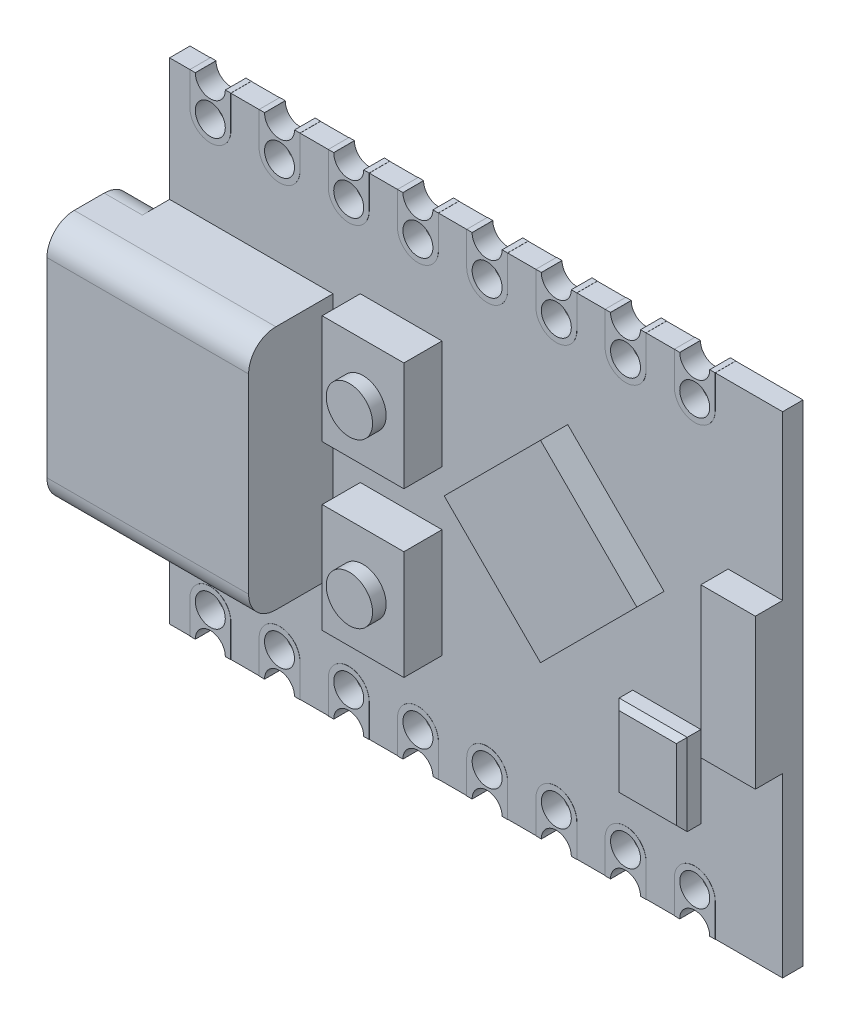
SolidWorks part; units mm, degrees
ref_plane "Plano frontal" through (0, 0, 0) normal (0, 0, 1) x (1, 0, 0)
ref_plane "Plano superior" through (0, 0, 0) normal (0, 1, 0) x (1, 0, 0)
ref_plane "Plano direito" through (0, 0, 0) normal (1, 0, 0) x (0, 0, -1)
sketch "Esboço1" plane through (0, 0, 0) normal (0, 0, 1) x (1, 0, 0)
  line L1 (-22.5, 18) -> (0, 18)
  line L2 (-22.5, 18) -> (-22.5, 0)
  line L3 (-22.5, 0) -> (0, 0)
  line L4 (0, 18) -> (0, 0)
  dimension "D1" = 18
  dimension "D2" = 22.5
extrude "PCI" add sketch "Esboço1" along normal blind 0.75
sketch "Esboço2" plane through (0, 0, 0.75) normal (0, 0, 1) x (1, 0, 0)
  line L0 (-11.4211, 10.1145) -> (-7.8855, 13.65)
  line L1 (-11.4211, 10.1145) -> (-7.8855, 6.5789)
  line L2 (-7.8855, 13.65) -> (-4.35, 10.1145)
  line L3 (-7.8855, 6.5789) -> (-4.35, 10.1145)
  line L4 (0, 0) -> (0, 18) construction
  line L5 (0, 18) -> (-22.5, 18) construction
  dimension "D1" = 45
  dimension "D2" = 4.35
  dimension "D3" = 4.35
  dimension "D4" = 5
extrude "ESP32" add sketch "Esboço2" along normal blind 1
sketch "Esboço3" plane through (0, 0, 0.75) normal (0, 0, 1) x (1, 0, 0)
  line L0 (-22.5, 18) -> (-22.5, 0) construction
  line L1 (-16.5, 13.5) -> (-23.9, 13.5)
  line L2 (-16.5, 13.5) -> (-16.5, 4.5)
  line L3 (-16.5, 4.5) -> (-23.9, 4.5)
  line L4 (-23.9, 13.5) -> (-23.9, 4.5)
  line L5 (-22.5, 9) -> (0, 9) construction
  line L6 (0, 0) -> (0, 18) construction
  dimension "D1" = 1.4
  dimension "D2" = 7.4
  dimension "D3" = 4.5
  dimension "D4" = 9
extrude "USB-C" add sketch "Esboço3" along normal blind 3.1
fillet "Arredondamento inferior USB" radius 1 2 edges at (-23.2, 13.5, 0.75) (-23.2, 4.5, 0.75)
fillet "Arredondamento Superior USB" radius 1 2 edges at (-20.2, 13.5, 3.85) (-20.2, 4.5, 3.85)
sketch "Esboço8" plane through (-23.9, 0, 0) normal (-1, 0, 0) x (0, 0, 1)
  line L0 (1.05, 12.5) -> (1.05, 5.5)
  line L1 (1.75, 4.8) -> (2.85, 4.8)
  line L2 (3.55, 5.5) -> (3.55, 12.5)
  line L3 (2.85, 13.2) -> (1.75, 13.2)
  line L4 (2.85, 13.5) -> (1.75, 13.5) construction
  line L5 (3.85, 12.5) -> (3.85, 5.5) construction
  arc A0 (1.75, 13.2) -> (1.05, 12.5) centre (1.75, 12.5) ccw
  arc A1 (1.05, 5.5) -> (1.75, 4.8) centre (1.75, 5.5) ccw
  arc A2 (2.85, 4.8) -> (3.55, 5.5) centre (2.85, 5.5) ccw
  arc A3 (3.55, 12.5) -> (2.85, 13.2) centre (2.85, 12.5) ccw
  dimension "D1" = 0.7
  dimension "D2" = 0.3
  dimension "D3" = 2.8
  dimension "D4" = 0.3
  dimension "D5" = 8.7
extrude "Furo USB" cut sketch "Esboço8" against normal blind 3.1
sketch "Esboço9" plane through (-23.9, 0, 0) normal (-1, 0, 0) x (0, 0, 1)
  line L0 (2.3, 13.2) -> (2.3, 4.8) construction
  line L1 (2.85, 13.2) -> (1.75, 13.2) construction
  line L2 (1.75, 4.8) -> (2.85, 4.8) construction
  line L3 (1.925, 5.4) -> (2.675, 5.4)
  line L4 (1.925, 5.4) -> (1.925, 12.6)
  line L5 (1.925, 12.6) -> (2.675, 12.6)
  line L6 (2.675, 5.4) -> (2.675, 12.6)
  line L7 (1.925, 5.4) -> (2.675, 12.6) construction
  line L8 (1.925, 12.6) -> (2.675, 5.4) construction
  point P4 (2.3, 9)
  dimension "D1" = 0.6
  dimension "D2" = 0.6
  dimension "D3" = 0.75
extrude "ConexaoUSB" add sketch "Esboço9" against normal up to next from offset 0.5 offset against normal yes
sketch "Esboço10" plane through (0, 0, 0.75) normal (0, 0, 1) x (1, 0, 0)
  line L0 (-22.5, 0) -> (0, 0) construction
  line L1 (-22.5, 4.5) -> (-22.5, 0) construction
  line L2 (-21, 1.2) -> (-21, -0.7241) construction
  line L3 (-21, 16.8) -> (-21, 18.7241) construction
  line L4 (0, 9) -> (-28.3512, 9) construction
  line L5 (0, 0) -> (0, 18) construction
  circle A0 centre (-21, 1.2) radius 0.55
  circle A1 centre (-21, 0) radius 0.55
  circle A2 centre (-18.46, 1.2) radius 0.55
  circle A3 centre (-18.46, 0) radius 0.55
  circle A4 centre (-15.92, 1.2) radius 0.55
  circle A5 centre (-15.92, 0) radius 0.55
  circle A6 centre (-13.38, 1.2) radius 0.55
  circle A7 centre (-13.38, 0) radius 0.55
  circle A8 centre (-10.84, 1.2) radius 0.55
  circle A9 centre (-10.84, 0) radius 0.55
  circle A10 centre (-8.3, 1.2) radius 0.55
  circle A11 centre (-8.3, 0) radius 0.55
  circle A12 centre (-5.76, 1.2) radius 0.55
  circle A13 centre (-5.76, 0) radius 0.55
  circle A14 centre (-3.22, 1.2) radius 0.55
  circle A15 centre (-3.22, 0) radius 0.55
  circle A16 centre (-3.22, 18) radius 0.55
  circle A17 centre (-3.22, 16.8) radius 0.55
  circle A18 centre (-5.76, 18) radius 0.55
  circle A19 centre (-5.76, 16.8) radius 0.55
  circle A20 centre (-8.3, 18) radius 0.55
  circle A21 centre (-8.3, 16.8) radius 0.55
  circle A22 centre (-10.84, 18) radius 0.55
  circle A23 centre (-10.84, 16.8) radius 0.55
  circle A24 centre (-13.38, 18) radius 0.55
  circle A25 centre (-13.38, 16.8) radius 0.55
  circle A26 centre (-15.92, 18) radius 0.55
  circle A27 centre (-15.92, 16.8) radius 0.55
  circle A28 centre (-18.46, 18) radius 0.55
  circle A29 centre (-18.46, 16.8) radius 0.55
  circle A30 centre (-21, 18) radius 0.55
  circle A31 centre (-21, 16.8) radius 0.55
  dimension "D1" = 1.2
  dimension "D2" = 1.1
  dimension "D7" = 2.54
  dimension "D3" = 0
  dimension "D4" = 1.5
  dimension "D5" = 8
extrude "FurosPCB" cut sketch "Esboço10" against normal up to next (0.75 mm away)
sketch "Esboço11" plane through (0, 0, 0.75) normal (0, 0, 1) x (1, 0, 0)
  line L0 (-21.75, 1.2) -> (-21.75, 0)
  line L1 (-20.25, 1.2) -> (-20.25, 0)
  line L2 (-17.71, 1.2) -> (-17.71, 0)
  line L4 (-21.75, 0) -> (-21.55, 0)
  line L5 (-20.45, 0) -> (-20.25, 0)
  line L6 (-17.91, 0) -> (-17.71, 0)
  line L7 (-19.21, 1.2) -> (-19.21, 0)
  line L8 (-19.21, 0) -> (-19.01, 0)
  line L9 (-15.17, 1.2) -> (-15.17, 0)
  line L10 (-15.37, 0) -> (-15.17, 0)
  line L11 (-16.67, 1.2) -> (-16.67, 0)
  line L12 (-16.67, 0) -> (-16.47, 0)
  line L13 (-12.63, 1.2) -> (-12.63, 0)
  line L14 (-12.83, 0) -> (-12.63, 0)
  line L15 (-14.13, 1.2) -> (-14.13, 0)
  line L16 (-14.13, 0) -> (-13.93, 0)
  line L17 (-10.09, 1.2) -> (-10.09, 0)
  line L18 (-10.29, 0) -> (-10.09, 0)
  line L19 (-11.59, 1.2) -> (-11.59, 0)
  line L20 (-11.59, 0) -> (-11.39, 0)
  line L21 (-7.55, 1.2) -> (-7.55, 0)
  line L22 (-7.75, 0) -> (-7.55, 0)
  line L23 (-9.05, 1.2) -> (-9.05, 0)
  line L24 (-9.05, 0) -> (-8.85, 0)
  line L25 (-5.01, 1.2) -> (-5.01, 0)
  line L26 (-5.21, 0) -> (-5.01, 0)
  line L27 (-6.51, 1.2) -> (-6.51, 0)
  line L28 (-6.51, 0) -> (-6.31, 0)
  line L29 (-2.47, 1.2) -> (-2.47, 0)
  line L30 (-2.67, 0) -> (-2.47, 0)
  line L31 (-3.97, 1.2) -> (-3.97, 0)
  line L32 (-3.97, 0) -> (-3.77, 0)
  line L33 (0, 9) -> (-27.4378, 9) construction
  line L34 (0, 0) -> (0, 18) construction
  line L35 (-3.97, 18) -> (-3.77, 18)
  line L36 (-3.97, 16.8) -> (-3.97, 18)
  line L37 (-2.67, 18) -> (-2.47, 18)
  line L38 (-2.47, 16.8) -> (-2.47, 18)
  line L39 (-6.51, 18) -> (-6.31, 18)
  line L40 (-6.51, 16.8) -> (-6.51, 18)
  line L41 (-5.21, 18) -> (-5.01, 18)
  line L42 (-5.01, 16.8) -> (-5.01, 18)
  line L43 (-9.05, 18) -> (-8.85, 18)
  line L44 (-9.05, 16.8) -> (-9.05, 18)
  line L45 (-7.75, 18) -> (-7.55, 18)
  line L46 (-7.55, 16.8) -> (-7.55, 18)
  line L47 (-11.59, 18) -> (-11.39, 18)
  line L48 (-11.59, 16.8) -> (-11.59, 18)
  line L49 (-10.29, 18) -> (-10.09, 18)
  line L50 (-10.09, 16.8) -> (-10.09, 18)
  line L51 (-14.13, 18) -> (-13.93, 18)
  line L52 (-14.13, 16.8) -> (-14.13, 18)
  line L53 (-12.83, 18) -> (-12.63, 18)
  line L54 (-12.63, 16.8) -> (-12.63, 18)
  line L55 (-16.67, 18) -> (-16.47, 18)
  line L56 (-16.67, 16.8) -> (-16.67, 18)
  line L57 (-15.37, 18) -> (-15.17, 18)
  line L58 (-15.17, 16.8) -> (-15.17, 18)
  line L59 (-19.21, 18) -> (-19.01, 18)
  line L60 (-19.21, 16.8) -> (-19.21, 18)
  line L61 (-17.91, 18) -> (-17.71, 18)
  line L62 (-20.45, 18) -> (-20.25, 18)
  line L63 (-21.75, 18) -> (-21.55, 18)
  line L64 (-17.71, 16.8) -> (-17.71, 18)
  line L65 (-20.25, 16.8) -> (-20.25, 18)
  line L66 (-21.75, 16.8) -> (-21.75, 18)
  arc A9 (-20.45, 0) -> (-21.55, 0) centre (-21, 0) ccw construction
  circle A10 centre (-21, 1.2) radius 0.75
  arc A11 (-20.25, 1.2) -> (-21.75, 1.2) centre (-21, 1.2) ccw
  arc A12 (-20.45, 0) -> (-21.55, 0) centre (-21, 0) ccw
  circle A13 centre (-21, 1.2) radius 0.55 construction
  circle A14 centre (-21, 1.2) radius 0.55
  arc A15 (-17.91, 0) -> (-19.01, 0) centre (-18.46, 0) ccw
  circle A16 centre (-18.46, 1.2) radius 0.55
  arc A17 (-17.71, 1.2) -> (-19.21, 1.2) centre (-18.46, 1.2) ccw
  arc A18 (-15.37, 0) -> (-16.47, 0) centre (-15.92, 0) ccw
  circle A19 centre (-15.92, 1.2) radius 0.55
  arc A20 (-15.17, 1.2) -> (-16.67, 1.2) centre (-15.92, 1.2) ccw
  arc A21 (-12.83, 0) -> (-13.93, 0) centre (-13.38, 0) ccw
  circle A22 centre (-13.38, 1.2) radius 0.55
  arc A23 (-12.63, 1.2) -> (-14.13, 1.2) centre (-13.38, 1.2) ccw
  arc A24 (-10.29, 0) -> (-11.39, 0) centre (-10.84, 0) ccw
  circle A25 centre (-10.84, 1.2) radius 0.55
  arc A26 (-10.09, 1.2) -> (-11.59, 1.2) centre (-10.84, 1.2) ccw
  arc A27 (-7.75, 0) -> (-8.85, 0) centre (-8.3, 0) ccw
  circle A28 centre (-8.3, 1.2) radius 0.55
  arc A29 (-7.55, 1.2) -> (-9.05, 1.2) centre (-8.3, 1.2) ccw
  arc A30 (-5.21, 0) -> (-6.31, 0) centre (-5.76, 0) ccw
  circle A31 centre (-5.76, 1.2) radius 0.55
  arc A32 (-5.01, 1.2) -> (-6.51, 1.2) centre (-5.76, 1.2) ccw
  arc A33 (-2.67, 0) -> (-3.77, 0) centre (-3.22, 0) ccw
  circle A34 centre (-3.22, 1.2) radius 0.55
  arc A35 (-2.47, 1.2) -> (-3.97, 1.2) centre (-3.22, 1.2) ccw
  arc A36 (-2.47, 16.8) -> (-3.97, 16.8) centre (-3.22, 16.8) cw
  circle A37 centre (-3.22, 16.8) radius 0.55
  arc A38 (-2.67, 18) -> (-3.77, 18) centre (-3.22, 18) cw
  arc A39 (-5.01, 16.8) -> (-6.51, 16.8) centre (-5.76, 16.8) cw
  circle A40 centre (-5.76, 16.8) radius 0.55
  arc A41 (-5.21, 18) -> (-6.31, 18) centre (-5.76, 18) cw
  arc A42 (-7.55, 16.8) -> (-9.05, 16.8) centre (-8.3, 16.8) cw
  circle A43 centre (-8.3, 16.8) radius 0.55
  arc A44 (-7.75, 18) -> (-8.85, 18) centre (-8.3, 18) cw
  arc A45 (-10.09, 16.8) -> (-11.59, 16.8) centre (-10.84, 16.8) cw
  circle A46 centre (-10.84, 16.8) radius 0.55
  arc A47 (-10.29, 18) -> (-11.39, 18) centre (-10.84, 18) cw
  arc A48 (-12.63, 16.8) -> (-14.13, 16.8) centre (-13.38, 16.8) cw
  circle A49 centre (-13.38, 16.8) radius 0.55
  arc A50 (-12.83, 18) -> (-13.93, 18) centre (-13.38, 18) cw
  arc A51 (-15.17, 16.8) -> (-16.67, 16.8) centre (-15.92, 16.8) cw
  circle A52 centre (-15.92, 16.8) radius 0.55
  arc A53 (-15.37, 18) -> (-16.47, 18) centre (-15.92, 18) cw
  arc A54 (-17.71, 16.8) -> (-19.21, 16.8) centre (-18.46, 16.8) cw
  circle A55 centre (-18.46, 16.8) radius 0.55
  arc A56 (-17.91, 18) -> (-19.01, 18) centre (-18.46, 18) cw
  circle A57 centre (-21, 16.8) radius 0.55
  arc A58 (-20.45, 18) -> (-21.55, 18) centre (-21, 18) cw
  arc A59 (-20.25, 16.8) -> (-21.75, 16.8) centre (-21, 16.8) cw
  dimension "D1" = 0.2
  dimension "D2" = 8
extrude "PADs" add sketch "Esboço11" along normal blind 0.005
sketch "Esboço13" plane through (0, 0, 0) normal (0, 0, -1) x (-1, 0, 0)
  line L0 (22.5, 0) -> (21.55, 0) construction
  line L1 (20.45, 0) -> (19.01, 0) construction
  line L2 (21.75, 0) -> (21.55, 0)
  line L3 (20.45, 0) -> (20.25, 0)
  line L4 (20.25, 1.2) -> (20.25, 0)
  line L5 (21.75, 1.2) -> (21.75, 0)
  line L6 (19.21, 1.2) -> (19.21, 0)
  line L7 (19.21, 0) -> (19.01, 0)
  line L8 (17.91, 0) -> (17.71, 0)
  line L9 (17.71, 1.2) -> (17.71, 0)
  line L10 (16.67, 1.2) -> (16.67, 0)
  line L11 (16.67, 0) -> (16.47, 0)
  line L12 (15.37, 0) -> (15.17, 0)
  line L13 (15.17, 1.2) -> (15.17, 0)
  line L14 (14.13, 1.2) -> (14.13, 0)
  line L15 (14.13, 0) -> (13.93, 0)
  line L16 (12.83, 0) -> (12.63, 0)
  line L17 (12.63, 1.2) -> (12.63, 0)
  line L18 (11.59, 1.2) -> (11.59, 0)
  line L19 (11.59, 0) -> (11.39, 0)
  line L20 (10.29, 0) -> (10.09, 0)
  line L21 (10.09, 1.2) -> (10.09, 0)
  line L22 (9.05, 1.2) -> (9.05, 0)
  line L23 (9.05, 0) -> (8.85, 0)
  line L24 (7.75, 0) -> (7.55, 0)
  line L25 (7.55, 1.2) -> (7.55, 0)
  line L26 (6.51, 1.2) -> (6.51, 0)
  line L27 (6.51, 0) -> (6.31, 0)
  line L28 (5.21, 0) -> (5.01, 0)
  line L29 (5.01, 1.2) -> (5.01, 0)
  line L30 (3.97, 1.2) -> (3.97, 0)
  line L31 (3.97, 0) -> (3.77, 0)
  line L32 (2.67, 0) -> (2.47, 0)
  line L33 (2.47, 1.2) -> (2.47, 0)
  line L34 (0, 9) -> (22.5, 9) construction
  line L35 (0, 0) -> (0, 18) construction
  line L36 (22.5, 18) -> (22.5, 0) construction
  line L37 (2.47, 16.8) -> (2.47, 18)
  line L38 (2.67, 18) -> (2.47, 18)
  line L39 (3.97, 18) -> (3.77, 18)
  line L40 (3.97, 16.8) -> (3.97, 18)
  line L41 (5.01, 16.8) -> (5.01, 18)
  line L42 (5.21, 18) -> (5.01, 18)
  line L43 (6.51, 18) -> (6.31, 18)
  line L44 (6.51, 16.8) -> (6.51, 18)
  line L45 (7.55, 16.8) -> (7.55, 18)
  line L46 (7.75, 18) -> (7.55, 18)
  line L47 (9.05, 18) -> (8.85, 18)
  line L48 (9.05, 16.8) -> (9.05, 18)
  line L49 (10.09, 16.8) -> (10.09, 18)
  line L50 (10.29, 18) -> (10.09, 18)
  line L51 (11.59, 18) -> (11.39, 18)
  line L52 (11.59, 16.8) -> (11.59, 18)
  line L53 (12.63, 16.8) -> (12.63, 18)
  line L54 (12.83, 18) -> (12.63, 18)
  line L55 (14.13, 18) -> (13.93, 18)
  line L56 (14.13, 16.8) -> (14.13, 18)
  line L57 (15.17, 16.8) -> (15.17, 18)
  line L58 (15.37, 18) -> (15.17, 18)
  line L59 (16.67, 18) -> (16.47, 18)
  line L60 (16.67, 16.8) -> (16.67, 18)
  line L61 (17.71, 16.8) -> (17.71, 18)
  line L62 (17.91, 18) -> (17.71, 18)
  line L63 (19.21, 18) -> (19.01, 18)
  line L64 (19.21, 16.8) -> (19.21, 18)
  line L65 (21.75, 16.8) -> (21.75, 18)
  line L66 (20.25, 16.8) -> (20.25, 18)
  line L67 (20.45, 18) -> (20.25, 18)
  line L68 (21.75, 18) -> (21.55, 18)
  circle A0 centre (21, 1.2) radius 0.55 construction
  arc A1 (21.55, 0) -> (20.45, 0) centre (21, 0) ccw construction
  circle A2 centre (21, 1.2) radius 0.55
  arc A3 (21.55, 0) -> (20.45, 0) centre (21, 0) ccw
  arc A4 (21.75, 1.2) -> (20.25, 1.2) centre (21, 1.2) ccw
  circle A5 centre (21, 1.2) radius 0.75 construction
  arc A6 (19.01, 0) -> (17.91, 0) centre (18.46, 0) ccw
  arc A7 (19.21, 1.2) -> (17.71, 1.2) centre (18.46, 1.2) ccw
  circle A8 centre (18.46, 1.2) radius 0.55
  arc A9 (16.47, 0) -> (15.37, 0) centre (15.92, 0) ccw
  arc A10 (16.67, 1.2) -> (15.17, 1.2) centre (15.92, 1.2) ccw
  circle A11 centre (15.92, 1.2) radius 0.55
  arc A12 (13.93, 0) -> (12.83, 0) centre (13.38, 0) ccw
  arc A13 (14.13, 1.2) -> (12.63, 1.2) centre (13.38, 1.2) ccw
  circle A14 centre (13.38, 1.2) radius 0.55
  arc A15 (11.39, 0) -> (10.29, 0) centre (10.84, 0) ccw
  arc A16 (11.59, 1.2) -> (10.09, 1.2) centre (10.84, 1.2) ccw
  circle A17 centre (10.84, 1.2) radius 0.55
  arc A18 (8.85, 0) -> (7.75, 0) centre (8.3, 0) ccw
  arc A19 (9.05, 1.2) -> (7.55, 1.2) centre (8.3, 1.2) ccw
  circle A20 centre (8.3, 1.2) radius 0.55
  arc A21 (6.31, 0) -> (5.21, 0) centre (5.76, 0) ccw
  arc A22 (6.51, 1.2) -> (5.01, 1.2) centre (5.76, 1.2) ccw
  circle A23 centre (5.76, 1.2) radius 0.55
  arc A24 (3.77, 0) -> (2.67, 0) centre (3.22, 0) ccw
  arc A25 (3.97, 1.2) -> (2.47, 1.2) centre (3.22, 1.2) ccw
  circle A26 centre (3.22, 1.2) radius 0.55
  circle A27 centre (3.22, 16.8) radius 0.55
  arc A28 (3.97, 16.8) -> (2.47, 16.8) centre (3.22, 16.8) cw
  arc A29 (3.77, 18) -> (2.67, 18) centre (3.22, 18) cw
  circle A30 centre (5.76, 16.8) radius 0.55
  arc A31 (6.51, 16.8) -> (5.01, 16.8) centre (5.76, 16.8) cw
  arc A32 (6.31, 18) -> (5.21, 18) centre (5.76, 18) cw
  circle A33 centre (8.3, 16.8) radius 0.55
  arc A34 (9.05, 16.8) -> (7.55, 16.8) centre (8.3, 16.8) cw
  arc A35 (8.85, 18) -> (7.75, 18) centre (8.3, 18) cw
  circle A36 centre (10.84, 16.8) radius 0.55
  arc A37 (11.59, 16.8) -> (10.09, 16.8) centre (10.84, 16.8) cw
  arc A38 (11.39, 18) -> (10.29, 18) centre (10.84, 18) cw
  circle A39 centre (13.38, 16.8) radius 0.55
  arc A40 (14.13, 16.8) -> (12.63, 16.8) centre (13.38, 16.8) cw
  arc A41 (13.93, 18) -> (12.83, 18) centre (13.38, 18) cw
  circle A42 centre (15.92, 16.8) radius 0.55
  arc A43 (16.67, 16.8) -> (15.17, 16.8) centre (15.92, 16.8) cw
  arc A44 (16.47, 18) -> (15.37, 18) centre (15.92, 18) cw
  circle A45 centre (18.46, 16.8) radius 0.55
  arc A46 (19.21, 16.8) -> (17.71, 16.8) centre (18.46, 16.8) cw
  arc A47 (19.01, 18) -> (17.91, 18) centre (18.46, 18) cw
  arc A48 (21.75, 16.8) -> (20.25, 16.8) centre (21, 16.8) cw
  arc A49 (21.55, 18) -> (20.45, 18) centre (21, 18) cw
  circle A50 centre (21, 16.8) radius 0.55
  dimension "D1" = 0.2
  dimension "D2" = 8
extrude "InferiorPads" add sketch "Esboço13" along normal blind 0.005
sketch "Esboço14" plane through (0, 18, 0) normal (0, 1, 0) x (1, 0, 0)
  line L0 (-21.75, 0.005) -> (-21.75, -0.755)
  line L1 (-21.75, -0.755) -> (-21.55, -0.755)
  line L2 (-21.55, -0.755) -> (-21.55, 0.005)
  line L3 (-21.55, 0.005) -> (-21.75, 0.005)
  line L4 (-20.45, 0.005) -> (-20.25, 0)
  line L5 (-20.25, 0) -> (-20.25, -0.755)
  line L6 (-20.25, -0.755) -> (-20.45, -0.755)
  line L7 (-20.45, -0.755) -> (-20.45, 0.005)
  line L8 (-19.21, 0.005) -> (-19.21, -0.755)
  line L9 (-19.01, 0.005) -> (-19.21, 0.005)
  line L10 (-19.01, -0.755) -> (-19.01, 0.005)
  line L11 (-19.21, -0.755) -> (-19.01, -0.755)
  line L12 (-17.91, -0.755) -> (-17.91, 0.005)
  line L13 (-17.91, 0.005) -> (-17.71, 0)
  line L14 (-17.71, 0) -> (-17.71, -0.755)
  line L15 (-17.71, -0.755) -> (-17.91, -0.755)
  line L16 (-16.67, 0.005) -> (-16.67, -0.755)
  line L17 (-16.47, 0.005) -> (-16.67, 0.005)
  line L18 (-16.47, -0.755) -> (-16.47, 0.005)
  line L19 (-16.67, -0.755) -> (-16.47, -0.755)
  line L20 (-15.37, -0.755) -> (-15.37, 0.005)
  line L21 (-15.37, 0.005) -> (-15.17, 0)
  line L22 (-15.17, 0) -> (-15.17, -0.755)
  line L23 (-15.17, -0.755) -> (-15.37, -0.755)
  line L24 (-14.13, 0.005) -> (-14.13, -0.755)
  line L25 (-13.93, 0.005) -> (-14.13, 0.005)
  line L26 (-13.93, -0.755) -> (-13.93, 0.005)
  line L27 (-14.13, -0.755) -> (-13.93, -0.755)
  line L28 (-12.83, -0.755) -> (-12.83, 0.005)
  line L29 (-12.83, 0.005) -> (-12.63, 0)
  line L30 (-12.63, 0) -> (-12.63, -0.755)
  line L31 (-12.63, -0.755) -> (-12.83, -0.755)
  line L32 (-11.59, 0.005) -> (-11.59, -0.755)
  line L33 (-11.39, 0.005) -> (-11.59, 0.005)
  line L34 (-11.39, -0.755) -> (-11.39, 0.005)
  line L35 (-11.59, -0.755) -> (-11.39, -0.755)
  line L36 (-10.29, -0.755) -> (-10.29, 0.005)
  line L37 (-10.29, 0.005) -> (-10.09, 0)
  line L38 (-10.09, 0) -> (-10.09, -0.755)
  line L39 (-10.09, -0.755) -> (-10.29, -0.755)
  line L40 (-9.05, 0.005) -> (-9.05, -0.755)
  line L41 (-8.85, 0.005) -> (-9.05, 0.005)
  line L42 (-8.85, -0.755) -> (-8.85, 0.005)
  line L43 (-9.05, -0.755) -> (-8.85, -0.755)
  line L44 (-7.75, -0.755) -> (-7.75, 0.005)
  line L45 (-7.75, 0.005) -> (-7.55, 0)
  line L46 (-7.55, 0) -> (-7.55, -0.755)
  line L47 (-7.55, -0.755) -> (-7.75, -0.755)
  line L48 (-6.51, 0.005) -> (-6.51, -0.755)
  line L49 (-6.31, 0.005) -> (-6.51, 0.005)
  line L50 (-6.31, -0.755) -> (-6.31, 0.005)
  line L51 (-6.51, -0.755) -> (-6.31, -0.755)
  line L52 (-5.21, -0.755) -> (-5.21, 0.005)
  line L53 (-5.21, 0.005) -> (-5.01, 0)
  line L54 (-5.01, 0) -> (-5.01, -0.755)
  line L55 (-5.01, -0.755) -> (-5.21, -0.755)
  line L56 (-3.97, 0.005) -> (-3.97, -0.755)
  line L57 (-3.77, 0.005) -> (-3.97, 0.005)
  line L58 (-3.77, -0.755) -> (-3.77, 0.005)
  line L59 (-3.97, -0.755) -> (-3.77, -0.755)
  line L60 (-2.67, -0.755) -> (-2.67, 0.005)
  line L61 (-2.67, 0.005) -> (-2.47, 0)
  line L62 (-2.47, 0) -> (-2.47, -0.755)
  line L63 (-2.47, -0.755) -> (-2.67, -0.755)
  dimension "D1" = 8
extrude "PADEx" add sketch "Esboço14" along normal blind 0.005
sketch "Esboço16" plane through (0, 0, 0) normal (0, -1, 0) x (1, 0, 0)
  line L0 (-21.75, 0.755) -> (-21.55, 0.755) construction
  line L1 (-21.75, 0.755) -> (-21.55, 0.755)
  line L2 (-21.75, 0.755) -> (-21.75, -0.005)
  line L3 (-21.75, -0.005) -> (-21.55, -0.005)
  line L4 (-21.55, 0.755) -> (-21.55, -0.005)
  line L5 (-20.45, -0.005) -> (-20.25, -0.005)
  line L6 (-20.45, -0.005) -> (-20.45, 0.755)
  line L7 (-20.45, 0.755) -> (-20.25, 0.755)
  line L8 (-20.25, -0.005) -> (-20.25, 0.755)
  line L9 (-21.75, 0.755) -> (-21.75, 0.75) construction
  line L10 (-17.71, -0.005) -> (-17.71, 0.755)
  line L11 (-17.91, -0.005) -> (-17.91, 0.755)
  line L12 (-17.91, -0.005) -> (-17.71, -0.005)
  line L13 (-17.91, 0.755) -> (-17.71, 0.755)
  line L14 (-19.21, 0.755) -> (-19.01, 0.755)
  line L15 (-19.21, 0.755) -> (-19.21, -0.005)
  line L16 (-19.21, -0.005) -> (-19.01, -0.005)
  line L17 (-19.01, 0.755) -> (-19.01, -0.005)
  line L18 (-15.17, -0.005) -> (-15.17, 0.755)
  line L19 (-15.37, -0.005) -> (-15.37, 0.755)
  line L20 (-15.37, -0.005) -> (-15.17, -0.005)
  line L21 (-15.37, 0.755) -> (-15.17, 0.755)
  line L22 (-16.67, 0.755) -> (-16.47, 0.755)
  line L23 (-16.67, 0.755) -> (-16.67, -0.005)
  line L24 (-16.67, -0.005) -> (-16.47, -0.005)
  line L25 (-16.47, 0.755) -> (-16.47, -0.005)
  line L26 (-12.63, -0.005) -> (-12.63, 0.755)
  line L27 (-12.83, -0.005) -> (-12.83, 0.755)
  line L28 (-12.83, -0.005) -> (-12.63, -0.005)
  line L29 (-12.83, 0.755) -> (-12.63, 0.755)
  line L30 (-14.13, 0.755) -> (-13.93, 0.755)
  line L31 (-14.13, 0.755) -> (-14.13, -0.005)
  line L32 (-14.13, -0.005) -> (-13.93, -0.005)
  line L33 (-13.93, 0.755) -> (-13.93, -0.005)
  line L34 (-10.09, -0.005) -> (-10.09, 0.755)
  line L35 (-10.29, -0.005) -> (-10.29, 0.755)
  line L36 (-10.29, -0.005) -> (-10.09, -0.005)
  line L37 (-10.29, 0.755) -> (-10.09, 0.755)
  line L38 (-11.59, 0.755) -> (-11.39, 0.755)
  line L39 (-11.59, 0.755) -> (-11.59, -0.005)
  line L40 (-11.59, -0.005) -> (-11.39, -0.005)
  line L41 (-11.39, 0.755) -> (-11.39, -0.005)
  line L42 (-7.55, -0.005) -> (-7.55, 0.755)
  line L43 (-7.75, -0.005) -> (-7.75, 0.755)
  line L44 (-7.75, -0.005) -> (-7.55, -0.005)
  line L45 (-7.75, 0.755) -> (-7.55, 0.755)
  line L46 (-9.05, 0.755) -> (-8.85, 0.755)
  line L47 (-9.05, 0.755) -> (-9.05, -0.005)
  line L48 (-9.05, -0.005) -> (-8.85, -0.005)
  line L49 (-8.85, 0.755) -> (-8.85, -0.005)
  line L50 (-5.01, -0.005) -> (-5.01, 0.755)
  line L51 (-5.21, -0.005) -> (-5.21, 0.755)
  line L52 (-5.21, -0.005) -> (-5.01, -0.005)
  line L53 (-5.21, 0.755) -> (-5.01, 0.755)
  line L54 (-6.51, 0.755) -> (-6.31, 0.755)
  line L55 (-6.51, 0.755) -> (-6.51, -0.005)
  line L56 (-6.51, -0.005) -> (-6.31, -0.005)
  line L57 (-6.31, 0.755) -> (-6.31, -0.005)
  line L58 (-2.47, -0.005) -> (-2.47, 0.755)
  line L59 (-2.67, -0.005) -> (-2.67, 0.755)
  line L60 (-2.67, -0.005) -> (-2.47, -0.005)
  line L61 (-2.67, 0.755) -> (-2.47, 0.755)
  line L62 (-3.97, 0.755) -> (-3.77, 0.755)
  line L63 (-3.97, 0.755) -> (-3.97, -0.005)
  line L64 (-3.97, -0.005) -> (-3.77, -0.005)
  line L65 (-3.77, 0.755) -> (-3.77, -0.005)
  dimension "D1" = 8
extrude "PADEx1" add sketch "Esboço16" along normal blind 0.005
sketch "Esboço17" plane through (0, 0, 0.75) normal (0, 0, 1) x (1, 0, 0)
  line L0 (0, 18) -> (-2.47, 18) construction
  line L1 (-2, 12) -> (0, 12)
  line L2 (-2, 12) -> (-2, 6.5)
  line L3 (-2, 6.5) -> (0, 6.5)
  line L4 (0, 12) -> (0, 6.5)
  line L5 (0, 0) -> (0, 18) construction
  dimension "D1" = 6
  dimension "D2" = 5.5
  dimension "D3" = 2
extrude "Antena" add sketch "Esboço17" along normal blind 1
sketch "Esboço18" plane through (0, 0, 0.75) normal (0, 0, 1) x (1, 0, 0)
  line L0 (-16.5, 4.5) -> (-16.5, 13.5) construction
  line L1 (-15.5, 14) -> (-12.5, 14)
  line L2 (-15.5, 14) -> (-15.5, 10)
  line L3 (-15.5, 10) -> (-12.5, 10)
  line L4 (-12.5, 14) -> (-12.5, 10)
  line L5 (-15.5, 8) -> (-12.5, 8)
  line L6 (-15.5, 8) -> (-15.5, 4)
  line L7 (-15.5, 4) -> (-12.5, 4)
  line L8 (-12.5, 8) -> (-12.5, 4)
  line L9 (-14.13, 18) -> (-15.17, 18) construction
  point P8 (-16.5, 9)
  dimension "D1" = 4
  dimension "D2" = 3
  dimension "D3" = 1
  dimension "D4" = 2
  dimension "D5" = 8
extrude "Buttons" add sketch "Esboço18" along normal blind 1.4
sketch "Esboço19" plane through (0, 0, 2.15) normal (0, 0, 1) x (1, 0, 0)
  line L0 (-12.5, 10) -> (-12.5, 14) construction
  line L2 (-12.5, 14) -> (-15.5, 14) construction
  line L4 (-12.5, 8) -> (-15.5, 8) construction
  line L5 (-12.5, 4) -> (-12.5, 8) construction
  circle A0 centre (-14, 6) radius 0.85
  circle A1 centre (-14, 12) radius 0.85
  dimension "D1" = 1.7
  dimension "D2" = 1.5
  dimension "D3" = 2
  dimension "D4" = 2
  dimension "D5" = 1.5
extrude "Ressalto-extrusão12" add sketch "Esboço19" along normal blind 0.5
sketch "Esboço20" plane through (0, 0, 0.75) normal (0, 0, 1) x (1, 0, 0)
  line L0 (-5.01, 0) -> (-3.97, 0) construction
  line L1 (-5.5, 6.4) -> (-3, 6.4)
  line L2 (-5.5, 6.4) -> (-5.5, 3.4)
  line L3 (-5.5, 3.4) -> (-3, 3.4)
  line L4 (-3, 6.4) -> (-3, 3.4)
  line L5 (0, 0) -> (0, 6.5) construction
  dimension "D1" = 3
  dimension "D2" = 2.5
  dimension "D3" = 3.4
  dimension "D4" = 3
extrude "Ressalto-extrusão13" add sketch "Esboço20" along normal blind 0.7
chamfer "Chanfro1" distance 0.2 angle 45 4 edges at (-4.25, 6.4, 1.45) (-3, 4.9, 1.45) (-4.25, 3.4, 1.45) (-5.5, 4.9, 1.45)
ref_plane "Plane1" through (0, 9, 0) normal (0, 1, 0) x (1, 0, 0)
